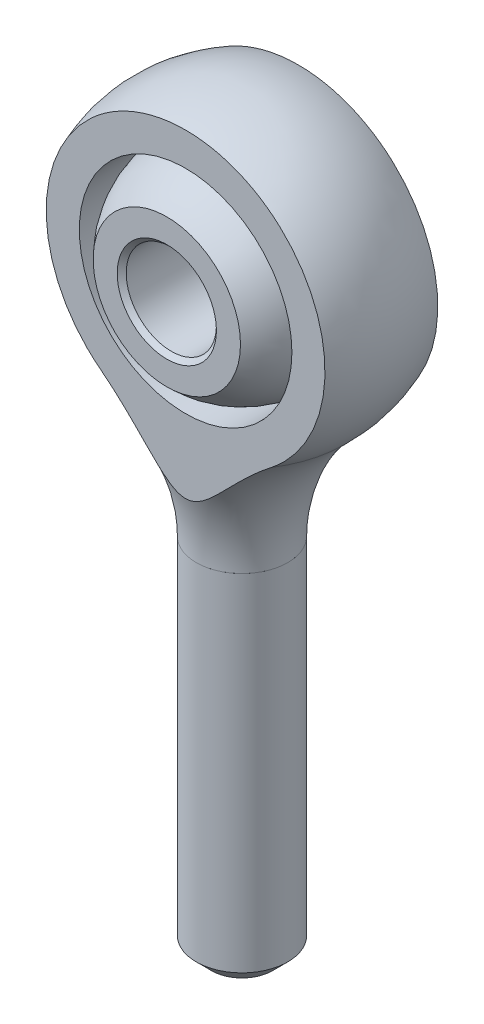
SolidWorks part; units mm, degrees
ref_plane "Front" through (0, 0, 0) normal (0, 0, 1) x (1, 0, 0)
ref_plane "Top" through (0, 0, 0) normal (0, 1, 0) x (1, 0, 0)
ref_plane "Right" through (0, 0, 0) normal (1, 0, 0) x (0, 0, -1)
sketch "Sketch1" plane through (0, 0, 0) normal (0, 0, 1) x (1, 0, 0)
  line L0 (0, 0) -> (0, -19.05)
  line L1 (0, -19.05) -> (2.413, -19.05)
  line L2 (2.413, -19.05) -> (2.413, 0)
  line L3 (2.413, 0) -> (0, 0)
  line L5 (0, 20.6375) -> (0, 0) construction
  line L6 (0, 20.6375) -> (7.9375, 20.6375) construction
  line L7 (7.9375, 20.6375) -> (7.9375, 12.7) construction
  line L8 (-2.413, -19.05) -> (-2.413, 0) construction
  line L9 (2.4991, -19.0003) -> (2.4991, -19.7953)
  line L10 (2.4991, -19.7953) -> (1.8106, -19.3978)
  line L11 (1.8966, -19.4475) -> (1.8966, -19.3481)
  line L12 (1.8106, -19.3978) -> (2.4991, -19.0003)
  line L13 (2.456, -19.0252) -> (2.456, -19.7705)
  line L14 (2.4991, -19.3978) -> (2.413, -19.3978)
  line L15 (2.413, -19.05) -> (2.413, -19.7456)
  line L16 (1.8106, -19.3978) -> (1.8966, -19.3978)
  arc A0 (5.4115, 6.8932) -> (0, 20.6375) centre (0, 12.7) ccw construction
  circle A1 centre (0, 12.7) radius 2.3812 construction
  circle A2 centre (0, 12.7) radius 5.5562 construction
  circle A3 centre (0, 12.7) radius 5.6118 construction
  arc A4 (2.413, 0) -> (5.4115, 6.8932) centre (11.8355, 0) cw construction
  point P24 (0, 18.2562)
  point P26 (2.413, -19.3978)
  point P28 (2.456, -19.3978)
  dimension "A" = 4.7625
  dimension "Ball Dia" = 11.1125
  dimension "B" = 15.875
  dimension "D1" = 11.2236
  dimension "D" = 31.75
  dimension "E" = 19.05
  dimension "Thread Dia" = 4.826
  dimension "D2" = 60
  dimension "Pitch" = 0.795
  dimension "D4" = 0.0994
sketch "Sketch2" plane through (0, 0, 0) normal (1, 0, 0) x (0, 0, -1)
  line L0 (2.9766, 12.7) -> (-2.9766, 12.7)
  line L1 (2.9766, 13.2248) -> (0, 12.7) construction
  line L2 (2.9766, 12.1752) -> (0, 12.7) construction
  line L6 (3.9688, 12.7) -> (-3.9687, 12.7)
  line L7 (0, 10.3187) -> (0, 15.0812)
  line L8 (0, 20.6375) -> (0, 0) construction
  line L9 (0, 15.0812) -> (0, 10.3187) construction
  circle A0 centre (0, 12.7) radius 5.5563
  circle A1 centre (0, 12.7) radius 7.9375
  point P4 (0, 12.7)
  point P7 (0, 18.2562)
  point P9 (0, 7.1437)
  point P14 (0, 12.7)
  point P18 (0, 12.7)
  point P23 (7.9375, 12.7)
  point P25 (-7.9375, 12.7)
  dimension "OAWidth" = 5.9531
  dimension "Swivel" = 20
  dimension "BallWidth" = 7.9375
sketch "Sketch15" plane through (0, 0, 0) normal (0, 0, 1) x (1, 0, 0)
  line L0 (0, 20.6375) -> (0, 0) construction
  line L1 (7.9375, 20.6375) -> (-7.9375, 20.6375)
  line L2 (7.9375, 20.6375) -> (7.9375, 0)
  line L3 (7.9375, 0) -> (-7.9375, 0)
  line L4 (-7.9375, 20.6375) -> (-7.9375, 0)
  line L5 (2.413, 0) -> (0, 0) construction
  point P5 (0, 20.6375)
sketch "Sketch14" plane through (0, 0, 0) normal (0, 0, 1) x (1, 0, 0)
  line L1 (0, 0) -> (0, -19.05) construction
  line L2 (0, -19.05) -> (2.413, -19.05) construction
  line L3 (2.413, -19.05) -> (2.413, 0) construction
  line L5 (0, 0) -> (0, -19.05)
  line L6 (0, -19.05) -> (2.413, -19.05)
  line L7 (2.413, -19.05) -> (2.413, 0)
  line L8 (2.413, 0) -> (0, 0) construction
  line L9 (2.413, 0) -> (0, 0)
revolve "Revolve4" add sketch "Sketch14" angle 360 about L0
sketch "Sketch21" plane through (0, 0, 0) normal (0, 0, 1) x (1, 0, 0)
  line L0 (0, 20.6375) -> (0, 0) construction
  line L1 (2.413, 0) -> (0, 0) construction
  line L2 (0, 20.6375) -> (0, 0)
  line L3 (2.413, 0) -> (0, 0)
  arc A0 (5.4115, 6.8932) -> (2.413, 0) centre (11.8355, 0) ccw construction
  arc A1 (5.4115, 6.8932) -> (0, 20.6375) centre (0, 12.7) ccw construction
  arc A2 (5.4115, 6.8932) -> (2.413, 0) centre (11.8355, 0) ccw
  arc A3 (5.4115, 6.8932) -> (0, 20.6375) centre (0, 12.7) ccw
revolve "Revolve5" add sketch "Sketch21" angle 360 about L0
sketch "Sketch24" plane through (0, 0, 0) normal (1, 0, 0) x (0, 0, -1)
  line L0 (2.9766, 12.7) -> (2.9766, 20.6375)
  line L1 (2.9766, 20.6375) -> (7.9375, 20.6375)
  line L2 (7.9375, 0) -> (7.9375, 20.6375)
  line L3 (2.9766, 12.7) -> (2.9766, 0.5953)
  line L4 (2.9766, 0.5953) -> (2.413, 0)
  line L5 (2.413, 0) -> (7.9375, 0)
  line L6 (0, 20.6375) -> (0, 0) construction
  line L7 (0, 20.6375) -> (0, 0) construction
  line L8 (-2.413, 0) -> (-7.9375, 0)
  line L9 (-2.9766, 0.5953) -> (-2.413, 0)
  line L10 (-2.9766, 12.7) -> (-2.9766, 0.5953)
  line L11 (-7.9375, 0) -> (-7.9375, 20.6375)
  line L12 (-2.9766, 20.6375) -> (-7.9375, 20.6375)
  line L13 (-2.9766, 12.7) -> (-2.9766, 20.6375)
  dimension "D1" = 0.5953
extrude "Cut-Extrude10" cut sketch "Sketch24" against normal through all both and the other way through all
sketch "Sketch17" plane through (0, 0, 0) normal (0, 0, 1) x (1, 0, 0)
  circle A2 centre (0, 12.7) radius 5.6118 construction
  circle A3 centre (0, 12.7) radius 5.6118
extrude "Cut-Extrude9" cut sketch "Sketch17" against normal through all both and the other way through all
sketch "Sketch7" plane through (0, 0, 0) normal (0, 0, 1) x (1, 0, 0)
  line L0 (0, 18.2562) -> (0, 7.1437)
  line L1 (0, 20.6375) -> (0, 0) construction
  line L2 (0, 0) -> (0, 7.1437) construction
  arc A0 (0, 7.1437) -> (0, 18.2562) centre (0, 12.7) ccw
  circle A1 centre (0, 12.7) radius 5.5562 construction
revolve "Revolve3" add sketch "Sketch7" angle 360 about L2
sketch "Sketch10" plane through (0, 0, 0) normal (0, 0, 1) x (1, 0, 0)
  circle A0 centre (0, 12.7) radius 2.3812 construction
  circle A1 centre (0, 12.7) radius 2.3812
extrude "Cut-Extrude4" cut sketch "Sketch10" against normal through all and the other way through all
sketch "Sketch22" plane through (0, 0, 0) normal (0, 0, 1) x (1, 0, 0)
  line L0 (-7.9375, 20.6375) -> (-7.9375, 0) construction
  line L1 (7.9375, 0) -> (-7.9375, 0) construction
  line L2 (7.9375, 20.6375) -> (7.9375, 0) construction
  line L3 (7.9375, 20.6375) -> (-7.9375, 20.6375) construction
  line L4 (-7.9375, 20.6375) -> (-7.9375, 0)
  line L5 (7.9375, 0) -> (-7.9375, 0)
  line L6 (7.9375, 20.6375) -> (7.9375, 0)
  line L7 (7.9375, 20.6375) -> (-7.9375, 20.6375)
extrude "Cut-Extrude7" cut sketch "Sketch22" against normal through all from vertex starting at point (0, 12.7, -3.9688)
sketch "Sketch23" plane through (0, 0, 0) normal (0, 0, 1) x (1, 0, 0)
  line L0 (-7.9375, 20.6375) -> (-7.9375, 0) construction
  line L1 (7.9375, 0) -> (-7.9375, 0) construction
  line L2 (7.9375, 20.6375) -> (7.9375, 0) construction
  line L3 (7.9375, 20.6375) -> (-7.9375, 20.6375) construction
  line L4 (-7.9375, 20.6375) -> (-7.9375, 0)
  line L5 (7.9375, 0) -> (-7.9375, 0)
  line L6 (7.9375, 20.6375) -> (7.9375, 0)
  line L7 (7.9375, 20.6375) -> (-7.9375, 20.6375)
extrude "Cut-Extrude8" cut sketch "Sketch23" along normal through all from vertex starting at point (0, 12.7, 3.9687)
chamfer "Chamfer1" distance 0.795 angle 45 1 edges at (-2.413, -19.05, 0)
chamfer "Chamfer2" distance 0.2381 angle 45 2 edges at (2.3813, 12.7, 3.9687) (2.3813, 12.7, -3.9688)
sketch "Sketch18" [suppressed] plane through (0, -19.05, 0) normal (0, -1, 0) x (1, 0, 0)
  circle A0 centre (0, 0) radius 2.413 construction
  circle A1 centre (0, 0) radius 2.413
curve "Helix/Spiral1" [suppressed] pitch 0.795 height 19.845 turns 24.9617
sketch "Sketch19" [suppressed] plane through (0, 0, 0) normal (0, 0, 1) x (1, 0, 0)
  line L0 (1.8966, -19.4475) -> (1.8966, -19.3481) construction
  line L1 (1.8106, -19.3978) -> (2.4991, -19.0003) construction
  line L2 (2.4991, -19.7953) -> (1.8106, -19.3978) construction
  line L3 (2.456, -19.0252) -> (2.456, -19.7705) construction
  line L4 (1.8966, -19.4475) -> (1.8966, -19.3481)
  line L5 (1.8966, -19.3481) -> (2.456, -19.0252)
  line L6 (2.456, -19.7705) -> (1.8966, -19.4475)
  line L7 (2.456, -19.0252) -> (2.456, -19.7705)
sweep "Cut-Sweep1" [suppressed] cut profiles "Sketch19" path "Helix/Spiral1"
ref_plane "Plane1" [suppressed] through (0, 0, 0) normal (0, 1, 0) x (1, 0, 0)
sketch "Sketch20" [suppressed] plane through (0, 0, 0) normal (0, 1, 0) x (1, 0, 0)
  circle A0 centre (0, 0) radius 2.413
extrude "Boss-Extrude2" [suppressed] add sketch "Sketch20" against normal through all draft 60
combine bodies "Combine1" [suppressed] operation type add bodies to combine 130 133
equation "\"D1@Sketch1\"=\"Ball Dia@Sketch1\"*1.01"
equation "\"D1\"= \"A@Sketch1\" / 20"
equation "\"D3\"= \"E@Sketch1\" + .2"
equation "\"D4@Sketch1\"=\"Pitch@Sketch1\"/8"
equation "\"D1@Chamfer1\"=\"Pitch@Sketch1\""
equation "\"D4@Helix/Spiral1\"=\"Pitch@Sketch1\""
equation "\"D3@Helix/Spiral1\"=\"E@Sketch1\"+\"Pitch@Sketch1\""
equation "\"D1@Chamfer2\"=\"A@Sketch1\"/20"
equation "\"D1@Sketch24\"=(\"OAWidth@Sketch2\"/2)/5"
